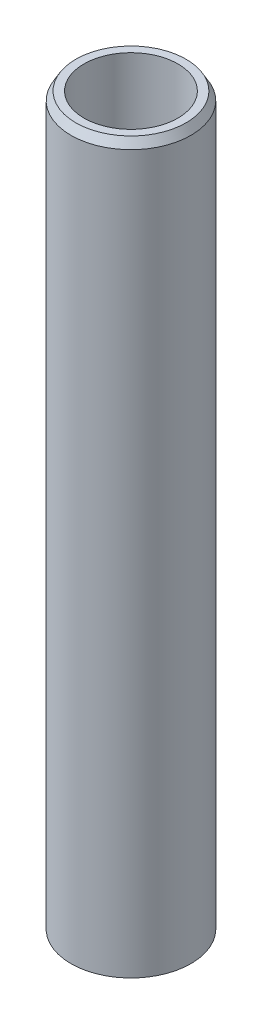
SolidWorks part; units mm, degrees
ref_plane "Front Plane" through (0, 0, 0) normal (0, 0, 1) x (1, 0, 0)
ref_plane "Top Plane" through (0, 0, 0) normal (0, 1, 0) x (1, 0, 0)
ref_plane "Right Plane" through (0, 0, 0) normal (1, 0, 0) x (0, 0, -1)
sketch "Sketch1" plane through (0, 0, 0) normal (0, 1, 0) x (1, 0, 0)
  circle A0 centre (0, 0) radius 25
  dimension "SHAFT_OD" = 50
extrude "Boss-Extrude1" add sketch "Sketch1" along normal blind 304.5086
sketch "Sketch2" plane through (0, 0, 0) normal (0, 1, 0) x (1, 0, 0)
  circle A0 centre (0, 0) radius 19.5837
  dimension "BORE_D" = 39.1675
extrude "Cut-Extrude1" cut sketch "Sketch2" along normal through all
chamfer "Chamfer1" distance 3.5099 angle 30 2 edges at (0, 304.5086, 25) (0, 0, 25) first distance on face at (0, 304.5086, 25) first distance on face at (0, 0, 19.5837)
